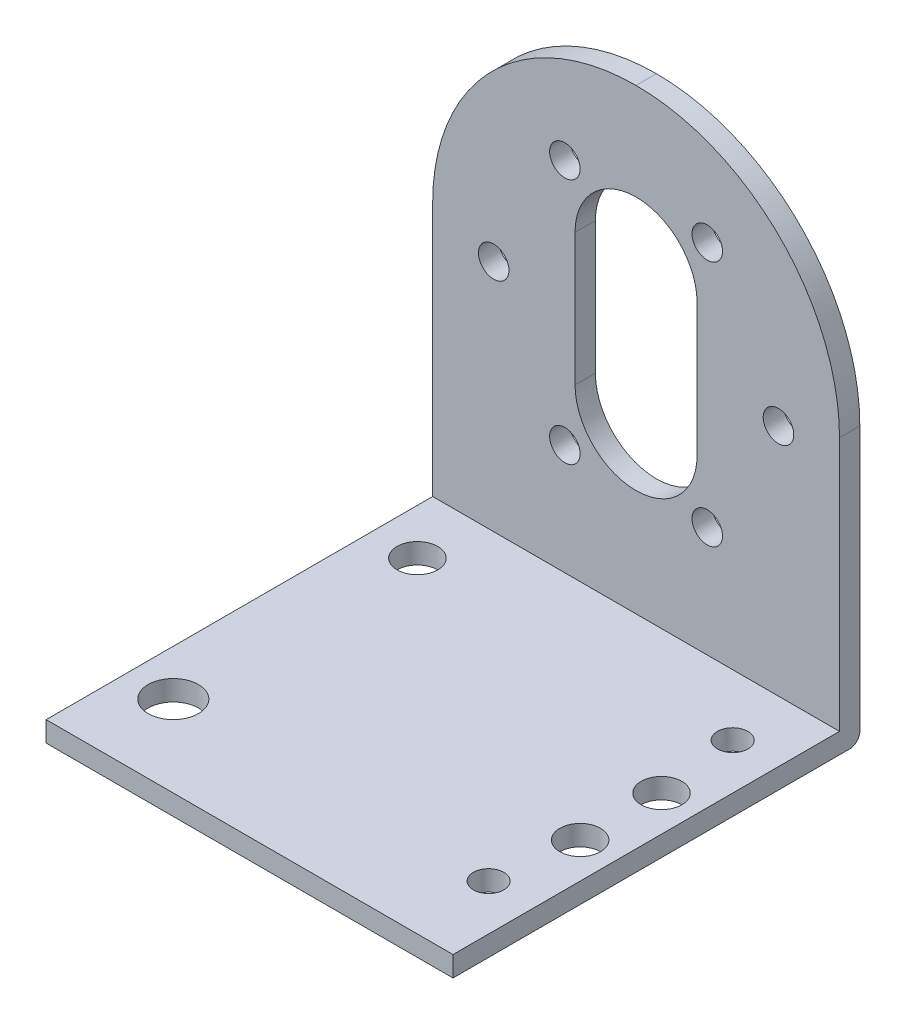
SolidWorks part; units mm, degrees
note: The reader was unsure of these and kept them because the rebuilt part matched: shared geometry of "Sketch1<5>".
ref_plane "前视基准面" through (0, 0, 0) normal (0, 0, 1) x (1, 0, 0)
ref_plane "上视基准面" through (0, 0, 0) normal (0, 1, 0) x (1, 0, 0)
ref_plane "右视基准面" through (0, 0, 0) normal (1, 0, 0) x (0, 0, -1)
other "Configuration Table"
sketch "Sketch1" plane through (0, 0, 0) normal (0, 1, 0) x (1, 0, 0)
  line L0 (-20, 18) -> (20, 18)
  line L5 (20, -20) -> (-20, -20)
  line L6 (20, -20) -> (20, 20)
  line L7 (20, 20) -> (-20, 20)
  line L8 (-20, -20) -> (-20, 20)
  line L9 (20, -20) -> (-20, 20) construction
  line L10 (20, 20) -> (-20, -20) construction
  line L11 (-20, 0) -> (20, 0) construction
  line L12 (0, 18) -> (0, -20) construction
  line L13 (-15.5, 12) -> (15.5, 12) construction
  line L14 (-15.5, 12) -> (-15.5, -12) construction
  circle A0 centre (15.5, -12) radius 1.5
  circle A1 centre (-15.5, -12) radius 1.5
  circle A2 centre (15.5, 12) radius 1.5
  circle A3 centre (-15.5, 12) radius 1.5
  circle A4 centre (-15.5, 12) radius 2
  circle A6 centre (-15.5, -12) radius 2.4749
  circle A7 centre (16.5, 4) radius 2
  circle A8 centre (16.5, -4) radius 2
  point P0 (0, 0)
  dimension "D4" = 3
  dimension "D7" = 8
  dimension "D1" = 40
  dimension "D2" = 40
  dimension "D3" = 2
  dimension "D5" = 4.5
  dimension "D6" = 8
  dimension "D8" = 32
extrude "Boss-Extrude3" add sketch "Sketch1" along normal blind 2 contours L8 L5 L6 L0 A3 A1 A0 A2
extrude "Boss-Extrude4" add sketch "Sketch1<5>" along normal blind 47 contours L8 L0 L6 L7
sketch "Sketch1<5>" plane through (0, 0, 0) normal (0, 1, 0) x (1, 0, 0) same geometry as "Sketch1"
sketch "Sketch2" plane through (0, 0, -18) normal (0, 0, 1) x (1, 0, 0)
  line L0 (0, 47) -> (0, 0) construction
  line L1 (-20, 47) -> (20, 47) construction
  line L2 (0, 31.5) -> (0, 18.5) construction
  line L9 (-20, 2) -> (20, 2) construction
  line L10 (14, 25) -> (7, 37.1244)
  line L11 (7, 37.1244) -> (-7, 37.1244)
  line L12 (-7, 37.1244) -> (-14, 25)
  line L13 (-14, 25) -> (-7, 12.8756)
  line L14 (-7, 12.8756) -> (7, 12.8756)
  line L15 (7, 12.8756) -> (14, 25)
  line L16 (6, 31.5) -> (6, 18.5)
  line L17 (-6, 31.5) -> (-6, 18.5)
  circle A0 centre (0, 25) radius 12.1244 construction
  circle A9 centre (-14, 25) radius 1.5
  circle A11 centre (-7, 37.1244) radius 1.5
  circle A12 centre (7, 37.1244) radius 1.5
  circle A13 centre (14, 25) radius 1.5
  circle A14 centre (7, 12.8756) radius 1.5
  circle A15 centre (-7, 12.8756) radius 1.5
  arc A16 (6, 31.5) -> (-6, 31.5) centre (0, 31.5) ccw
  arc A17 (-6, 18.5) -> (6, 18.5) centre (0, 18.5) ccw
  point P23 (0, 25)
  dimension "D1" = 23
  dimension "D2" = 28
fillet "Fillet1" radius 20 2 edges at (20, 47, -19) (-20, 47, -19)
fillet "Fillet2" radius 1 1 edges at (0, 0, -20)
extrude "Cut-Extrude2" cut sketch "Sketch2" against normal blind 47 contours L17 A17 L14 L16 A16 L11 | L14 A17 | L10 A12 L11 | L11 A12 L10 | L11 A11 L12 | L12 A11 L11 | L15 A13 L10 | L10 A13 L15 | L14 A14 L15 | L15 A14 L14 | L13 A15 L14 | L14 A15 L13 | L12 A9 L13 | L13 A9 L12
